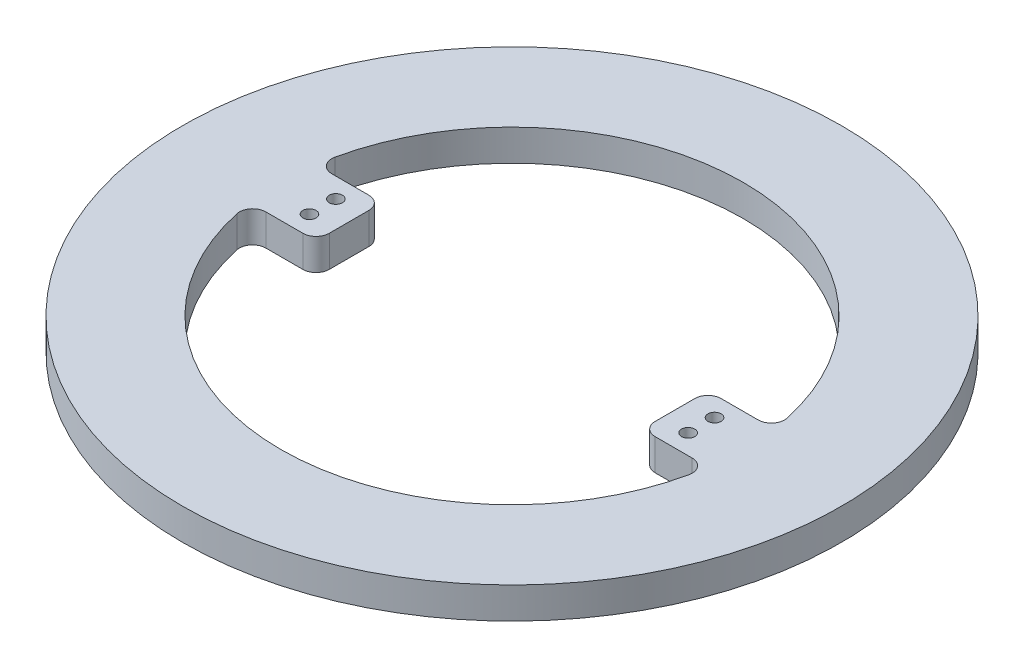
SolidWorks part; units mm, degrees
note: '?' marks a value the reader was unsure of.
ref_plane "Front Plane" through (0, 0, 0) normal (0, 0, 1) x (1, 0, 0)
ref_plane "Top Plane" through (0, 0, 0) normal (0, 1, 0) x (1, 0, 0)
ref_plane "Right Plane" through (0, 0, 0) normal (1, 0, 0) x (0, 0, -1)
sketch "Sketch1" plane through (0, 0, 0) normal (0, 1, 0) x (1, 0, 0)
  line L0 (0, -12.4783) -> (0, 12.4783) construction
  line L2 (-12.5, 0) -> (12.5, 0) construction
  line L6 (-32.3068, -5) -> (-26.6981, -5)
  line L7 (-49.95, 0) -> (49.95, 0) construction
  line L9 (0, 49.95) -> (0, -49.95) construction
  line L11 (-32.3068, 5) -> (-26.6981, 5)
  line L12 (-24.6981, 3) -> (-24.6981, -3)
  line L13 (24.6981, 3) -> (24.6981, -3)
  line L14 (26.6981, -5) -> (32.3068, -5)
  line L15 (26.6981, 5) -> (32.3068, 5)
  circle A0 centre (0, 0) radius 49.95
  arc A22 (-34.2615, -7.4235) -> (34.2615, -7.4235) centre (0, 0) ccw
  arc A23 (34.2615, 7.4235) -> (-34.2615, 7.4235) centre (0, 0) ccw
  arc A24 (32.3068, -5) -> (34.2615, -7.4235) centre (32.3068, -7) cw
  arc A25 (32.3068, 5) -> (34.2615, 7.4235) centre (32.3068, 7) ccw
  arc A26 (24.6981, 3) -> (26.6981, 5) centre (26.6981, 3) cw
  arc A27 (24.6981, -3) -> (26.6981, -5) centre (26.6981, -3) ccw
  arc A28 (-24.6981, 3) -> (-26.6981, 5) centre (-26.6981, 3) ccw
  arc A29 (-32.3068, 5) -> (-34.2615, 7.4235) centre (-32.3068, 7) cw
  arc A30 (-32.3068, -5) -> (-34.2615, -7.4235) centre (-32.3068, -7) ccw
  arc A31 (-24.6981, -3) -> (-26.6981, -5) centre (-26.6981, -3) cw
  circle A32 centre (-28.6981, -2) radius 1
  circle A33 centre (-28.6981, 2) radius 1
  circle A34 centre (28.6981, -2) radius 1
  circle A35 centre (28.6981, 2) radius 1
  point P7 (0, 0)
  point P12 (0, 0)
  point P20 (34.6981, -5)
  point P23 (34.6981, 5)
  point P26 (24.6981, 5)
  point P32 (24.6981, -5)
  point P35 (-24.6981, 5)
  point P38 (-34.6981, 5)
  point P41 (-34.6981, -5)
  point P44 (-24.6981, -5)
  dimension "D1" = 5
  dimension "D2" = 10
  dimension "D3" = 2
  dimension "D4" = 4
  dimension "D5" = 3
extrude "Boss-Extrude1" add sketch "Sketch1" along normal blind 4.75
sketch "Sketch2" plane through (0, 4.75, 0) normal (0, 1, 0) x (1, 0, 0)
  line L1 (0, 49.95) -> (0, -49.95) construction
  line L9 (-49.95, 0) -> (49.95, 0) construction
  circle A6 centre (0, 0) radius 49.95 construction
sketch "Sketch3" plane through (0, 4.75, 0) normal (0, 1, 0) x (1, 0, 0)
  line L0 (0, 35.0565) -> (0, 40.0565)
  line L1 (0.6118, 35.0511) -> (0.6991, 40.0504)
  line L2 (1.2235, 35.0351) -> (1.398, 40.0321)
  line L3 (1.8347, 35.0084) -> (2.0964, 40.0016)
  line L4 (2.4454, 34.9711) -> (2.7942, 39.9589)
  line L5 (3.0554, 34.9231) -> (3.4912, 39.9041)
  line L6 (3.6644, 34.8644) -> (4.187, 39.8371)
  line L7 (4.2723, 34.7952) -> (4.8817, 39.7579)
  line L8 (4.8789, 34.7153) -> (5.5748, 39.6667)
  line L9 (5.484, 34.6249) -> (6.2662, 39.5633)
  line L10 (6.0875, 34.5239) -> (6.9557, 39.4479)
  line L11 (6.6891, 34.4124) -> (7.6431, 39.3205)
  line L12 (7.2887, 34.2904) -> (8.3282, 39.1812)
  line L13 (7.886, 34.158) -> (9.0107, 39.0298)
  line L14 (8.4809, 34.0152) -> (9.6905, 38.8666)
  line L15 (9.0733, 33.862) -> (10.3674, 38.6916)
  line L16 (9.6629, 33.6985) -> (11.0411, 38.5048)
  line L17 (10.2495, 33.5247) -> (11.7114, 38.3062)
  line L18 (10.833, 33.3407) -> (12.3781, 38.096)
  line L19 (11.4133, 33.1466) -> (13.0411, 37.8742)
  line L20 (11.99, 32.9423) -> (13.7001, 37.6408)
  line L21 (12.5631, 32.728) -> (14.355, 37.396)
  line L22 (13.1324, 32.5038) -> (15.0054, 37.1397)
  line L23 (13.6977, 32.2697) -> (15.6513, 36.8722)
  line L24 (14.2588, 32.0257) -> (16.2924, 36.5934)
  line L25 (14.8155, 31.772) -> (16.9286, 36.3035)
  line L26 (15.3678, 31.5086) -> (17.5596, 36.0025)
  line L27 (15.9153, 31.2356) -> (18.1853, 35.6906)
  line L28 (16.458, 30.953) -> (18.8054, 35.3678)
  line L29 (16.9957, 30.6611) -> (19.4198, 35.0342)
  line L30 (17.5282, 30.3598) -> (20.0282, 34.6899)
  line L31 (18.0554, 30.0493) -> (20.6306, 34.3351)
  line L32 (18.5771, 29.7296) -> (21.2267, 33.9698)
  line L33 (19.0931, 29.4008) -> (21.8163, 33.5942)
  line L34 (19.6033, 29.0631) -> (22.3993, 33.2083)
  line L35 (20.1076, 28.7166) -> (22.9755, 32.8124)
  line L36 (20.6057, 28.3613) -> (23.5446, 32.4064)
  line L37 (21.0975, 27.9974) -> (24.1066, 31.9905)
  line L38 (21.5829, 27.6249) -> (24.6612, 31.5649)
  line L39 (22.0618, 27.244) -> (25.2084, 31.1297)
  line L40 (22.5339, 26.8548) -> (25.7478, 30.685)
  line L41 (22.9991, 26.4575) -> (26.2794, 30.231)
  line L42 (23.4574, 26.052) -> (26.803, 29.7678)
  line L43 (23.9085, 25.6387) -> (27.3185, 29.2955)
  line L44 (24.3523, 25.2175) -> (27.8256, 28.8142)
  line L45 (24.7887, 24.7887) -> (28.3242, 28.3242)
  line L46 (25.2175, 24.3523) -> (28.8142, 27.8256)
  line L47 (25.6387, 23.9085) -> (29.2955, 27.3185)
  line L48 (26.052, 23.4574) -> (29.7678, 26.803)
  line L49 (26.4575, 22.9991) -> (30.231, 26.2794)
  line L50 (26.8548, 22.5339) -> (30.685, 25.7478)
  line L51 (27.244, 22.0618) -> (31.1297, 25.2084)
  line L52 (27.6249, 21.5829) -> (31.5649, 24.6612)
  line L53 (27.9974, 21.0975) -> (31.9905, 24.1066)
  line L54 (28.3613, 20.6057) -> (32.4064, 23.5446)
  line L55 (28.7166, 20.1076) -> (32.8124, 22.9755)
  line L56 (29.0631, 19.6033) -> (33.2083, 22.3993)
  line L57 (29.4008, 19.0931) -> (33.5942, 21.8163)
  line L58 (29.7296, 18.5771) -> (33.9698, 21.2267)
  line L59 (30.0493, 18.0554) -> (34.3351, 20.6306)
  line L60 (30.3598, 17.5282) -> (34.6899, 20.0282)
  line L61 (30.6611, 16.9957) -> (35.0342, 19.4198)
  line L62 (30.953, 16.458) -> (35.3678, 18.8054)
  line L63 (31.2356, 15.9153) -> (35.6906, 18.1853)
  line L64 (31.5086, 15.3678) -> (36.0025, 17.5596)
  line L65 (31.772, 14.8155) -> (36.3035, 16.9286)
  line L66 (32.0257, 14.2588) -> (36.5934, 16.2924)
  line L67 (32.2697, 13.6977) -> (36.8722, 15.6513)
  line L68 (32.5038, 13.1324) -> (37.1397, 15.0054)
  line L69 (32.728, 12.5631) -> (37.396, 14.355)
  line L70 (32.9423, 11.99) -> (37.6408, 13.7001)
  line L71 (33.1466, 11.4133) -> (37.8742, 13.0411)
  line L72 (33.3407, 10.833) -> (38.096, 12.3781)
  line L73 (33.5247, 10.2495) -> (38.3062, 11.7114)
  line L74 (33.6985, 9.6629) -> (38.5048, 11.0411)
  line L75 (33.862, 9.0733) -> (38.6916, 10.3674)
  line L76 (34.0152, 8.4809) -> (38.8666, 9.6905)
  line L77 (34.158, 7.886) -> (39.0298, 9.0107)
  line L78 (34.2904, 7.2887) -> (39.1812, 8.3282)
  line L79 (34.4124, 6.6891) -> (39.3205, 7.6431)
  line L80 (34.5239, 6.0875) -> (39.4479, 6.9557)
  line L81 (34.6249, 5.484) -> (39.5633, 6.2662)
  line L82 (34.7153, 4.8789) -> (39.6667, 5.5748)
  line L83 (34.7952, 4.2723) -> (39.7579, 4.8817)
  line L84 (34.8644, 3.6644) -> (39.8371, 4.187)
  line L85 (34.9231, 3.0554) -> (39.9041, 3.4912)
  line L86 (34.9711, 2.4454) -> (39.9589, 2.7942)
  line L87 (35.0084, 1.8347) -> (40.0016, 2.0964)
  line L88 (35.0351, 1.2235) -> (40.0321, 1.398)
  line L89 (35.0511, 0.6118) -> (40.0504, 0.6991)
  line L90 (35.0565, 0) -> (40.0565, 0)
  line L91 (35.0511, -0.6118) -> (40.0504, -0.6991)
  line L92 (35.0351, -1.2235) -> (40.0321, -1.398)
  line L93 (35.0084, -1.8347) -> (40.0016, -2.0964)
  line L94 (34.9711, -2.4454) -> (39.9589, -2.7942)
  line L95 (34.9231, -3.0554) -> (39.9041, -3.4912)
  line L96 (34.8644, -3.6644) -> (39.8371, -4.187)
  line L97 (34.7952, -4.2723) -> (39.7579, -4.8817)
  line L98 (34.7153, -4.8789) -> (39.6667, -5.5748)
  line L99 (34.6249, -5.484) -> (39.5633, -6.2662)
  line L100 (34.5239, -6.0875) -> (39.4479, -6.9557)
  line L101 (34.4124, -6.6891) -> (39.3205, -7.6431)
  line L102 (34.2904, -7.2887) -> (39.1812, -8.3282)
  line L103 (34.158, -7.886) -> (39.0298, -9.0107)
  line L104 (34.0152, -8.4809) -> (38.8666, -9.6905)
  line L105 (33.862, -9.0733) -> (38.6916, -10.3674)
  line L106 (33.6985, -9.6629) -> (38.5048, -11.0411)
  line L107 (33.5247, -10.2495) -> (38.3062, -11.7114)
  line L108 (33.3407, -10.833) -> (38.096, -12.3781)
  line L109 (33.1466, -11.4133) -> (37.8742, -13.0411)
  line L110 (32.9423, -11.99) -> (37.6408, -13.7001)
  line L111 (32.728, -12.5631) -> (37.396, -14.355)
  line L112 (32.5038, -13.1324) -> (37.1397, -15.0054)
  line L113 (32.2697, -13.6977) -> (36.8722, -15.6513)
  line L114 (32.0257, -14.2588) -> (36.5934, -16.2924)
  line L115 (31.772, -14.8155) -> (36.3035, -16.9286)
  line L116 (31.5086, -15.3678) -> (36.0025, -17.5596)
  line L117 (31.2356, -15.9153) -> (35.6906, -18.1853)
  line L118 (30.953, -16.458) -> (35.3678, -18.8054)
  line L119 (30.6611, -16.9957) -> (35.0342, -19.4198)
  line L120 (30.3598, -17.5282) -> (34.6899, -20.0282)
  line L121 (30.0493, -18.0554) -> (34.3351, -20.6306)
  line L122 (29.7296, -18.5771) -> (33.9698, -21.2267)
  line L123 (29.4008, -19.0931) -> (33.5942, -21.8163)
  line L124 (29.0631, -19.6033) -> (33.2083, -22.3993)
  line L125 (28.7166, -20.1076) -> (32.8124, -22.9755)
  line L126 (28.3613, -20.6057) -> (32.4064, -23.5446)
  line L127 (27.9974, -21.0975) -> (31.9905, -24.1066)
  line L128 (27.6249, -21.5829) -> (31.5649, -24.6612)
  line L129 (27.244, -22.0618) -> (31.1297, -25.2084)
  line L130 (26.8548, -22.5339) -> (30.685, -25.7478)
  line L131 (26.4575, -22.9991) -> (30.231, -26.2794)
  line L132 (26.052, -23.4574) -> (29.7678, -26.803)
  line L133 (25.6387, -23.9085) -> (29.2955, -27.3185)
  line L134 (25.2175, -24.3523) -> (28.8142, -27.8256)
  line L135 (24.7887, -24.7887) -> (28.3242, -28.3242)
  line L136 (24.3523, -25.2175) -> (27.8256, -28.8142)
  line L137 (23.9085, -25.6387) -> (27.3185, -29.2955)
  line L138 (23.4574, -26.052) -> (26.803, -29.7678)
  line L139 (22.9991, -26.4575) -> (26.2794, -30.231)
  line L140 (22.5339, -26.8548) -> (25.7478, -30.685)
  line L141 (22.0618, -27.244) -> (25.2084, -31.1297)
  line L142 (21.5829, -27.6249) -> (24.6612, -31.5649)
  line L143 (21.0975, -27.9974) -> (24.1066, -31.9905)
  line L144 (20.6057, -28.3613) -> (23.5446, -32.4064)
  line L145 (20.1076, -28.7166) -> (22.9755, -32.8124)
  line L146 (19.6033, -29.0631) -> (22.3993, -33.2083)
  line L147 (19.0931, -29.4008) -> (21.8163, -33.5942)
  line L148 (18.5771, -29.7296) -> (21.2267, -33.9698)
  line L149 (18.0554, -30.0493) -> (20.6306, -34.3351)
  line L150 (17.5282, -30.3598) -> (20.0282, -34.6899)
  line L151 (16.9957, -30.6611) -> (19.4198, -35.0342)
  line L152 (16.458, -30.953) -> (18.8054, -35.3678)
  line L153 (15.9153, -31.2356) -> (18.1853, -35.6906)
  line L154 (15.3678, -31.5086) -> (17.5596, -36.0025)
  line L155 (14.8155, -31.772) -> (16.9286, -36.3035)
  line L156 (14.2588, -32.0257) -> (16.2924, -36.5934)
  line L157 (13.6977, -32.2697) -> (15.6513, -36.8722)
  line L158 (13.1324, -32.5038) -> (15.0054, -37.1397)
  line L159 (12.5631, -32.728) -> (14.355, -37.396)
  line L160 (11.99, -32.9423) -> (13.7001, -37.6408)
  line L161 (11.4133, -33.1466) -> (13.0411, -37.8742)
  line L162 (10.833, -33.3407) -> (12.3781, -38.096)
  line L163 (10.2495, -33.5247) -> (11.7114, -38.3062)
  line L164 (9.6629, -33.6985) -> (11.0411, -38.5048)
  line L165 (9.0733, -33.862) -> (10.3674, -38.6916)
  line L166 (8.4809, -34.0152) -> (9.6905, -38.8666)
  line L167 (7.886, -34.158) -> (9.0107, -39.0298)
  line L168 (7.2887, -34.2904) -> (8.3282, -39.1812)
  line L169 (6.6891, -34.4124) -> (7.6431, -39.3205)
  line L170 (6.0875, -34.5239) -> (6.9557, -39.4479)
  line L171 (5.484, -34.6249) -> (6.2662, -39.5633)
  line L172 (4.8789, -34.7153) -> (5.5748, -39.6667)
  line L173 (4.2723, -34.7952) -> (4.8817, -39.7579)
  line L174 (3.6644, -34.8644) -> (4.187, -39.8371)
  line L175 (3.0554, -34.9231) -> (3.4912, -39.9041)
  line L176 (2.4454, -34.9711) -> (2.7942, -39.9589)
  line L177 (1.8347, -35.0084) -> (2.0964, -40.0016)
  line L178 (1.2235, -35.0351) -> (1.398, -40.0321)
  line L179 (0.6118, -35.0511) -> (0.6991, -40.0504)
  line L180 (0, -35.0565) -> (0, -40.0565)
  line L181 (-0.6118, -35.0511) -> (-0.6991, -40.0504)
  line L182 (-1.2235, -35.0351) -> (-1.398, -40.0321)
  line L183 (-1.8347, -35.0084) -> (-2.0964, -40.0016)
  line L184 (-2.4454, -34.9711) -> (-2.7942, -39.9589)
  line L185 (-3.0554, -34.9231) -> (-3.4912, -39.9041)
  line L186 (-3.6644, -34.8644) -> (-4.187, -39.8371)
  line L187 (-4.2723, -34.7952) -> (-4.8817, -39.7579)
  line L188 (-4.8789, -34.7153) -> (-5.5748, -39.6667)
  line L189 (-5.484, -34.6249) -> (-6.2662, -39.5633)
  line L190 (-6.0875, -34.5239) -> (-6.9557, -39.4479)
  line L191 (-6.6891, -34.4124) -> (-7.6431, -39.3205)
  line L192 (-7.2887, -34.2904) -> (-8.3282, -39.1812)
  line L193 (-7.886, -34.158) -> (-9.0107, -39.0298)
  line L194 (-8.4809, -34.0152) -> (-9.6905, -38.8666)
  line L195 (-9.0733, -33.862) -> (-10.3674, -38.6916)
  line L196 (-9.6629, -33.6985) -> (-11.0411, -38.5048)
  line L197 (-10.2495, -33.5247) -> (-11.7114, -38.3062)
  line L198 (-10.833, -33.3407) -> (-12.3781, -38.096)
  line L199 (-11.4133, -33.1466) -> (-13.0411, -37.8742)
  line L200 (-11.99, -32.9423) -> (-13.7001, -37.6408)
  line L201 (-12.5631, -32.728) -> (-14.355, -37.396)
  line L202 (-13.1324, -32.5038) -> (-15.0054, -37.1397)
  line L203 (-13.6977, -32.2697) -> (-15.6513, -36.8722)
  line L204 (-14.2588, -32.0257) -> (-16.2924, -36.5934)
  line L205 (-14.8155, -31.772) -> (-16.9286, -36.3035)
  line L206 (-15.3678, -31.5086) -> (-17.5596, -36.0025)
  line L207 (-15.9153, -31.2356) -> (-18.1853, -35.6906)
  line L208 (-16.458, -30.953) -> (-18.8054, -35.3678)
  line L209 (-16.9957, -30.6611) -> (-19.4198, -35.0342)
  line L210 (-17.5282, -30.3598) -> (-20.0282, -34.6899)
  line L211 (-18.0554, -30.0493) -> (-20.6306, -34.3351)
  line L212 (-18.5771, -29.7296) -> (-21.2267, -33.9698)
  line L213 (-19.0931, -29.4008) -> (-21.8163, -33.5942)
  line L214 (-19.6033, -29.0631) -> (-22.3993, -33.2083)
  line L215 (-20.1076, -28.7166) -> (-22.9755, -32.8124)
  line L216 (-20.6057, -28.3613) -> (-23.5446, -32.4064)
  line L217 (-21.0975, -27.9974) -> (-24.1066, -31.9905)
  line L218 (-21.5829, -27.6249) -> (-24.6612, -31.5649)
  line L219 (-22.0618, -27.244) -> (-25.2084, -31.1297)
  line L220 (-22.5339, -26.8548) -> (-25.7478, -30.685)
  line L221 (-22.9991, -26.4575) -> (-26.2794, -30.231)
  line L222 (-23.4574, -26.052) -> (-26.803, -29.7678)
  line L223 (-23.9085, -25.6387) -> (-27.3185, -29.2955)
  line L224 (-24.3523, -25.2175) -> (-27.8256, -28.8142)
  line L225 (-24.7887, -24.7887) -> (-28.3242, -28.3242)
  line L226 (-25.2175, -24.3523) -> (-28.8142, -27.8256)
  line L227 (-25.6387, -23.9085) -> (-29.2955, -27.3185)
  line L228 (-26.052, -23.4574) -> (-29.7678, -26.803)
  line L229 (-26.4575, -22.9991) -> (-30.231, -26.2794)
  line L230 (-26.8548, -22.5339) -> (-30.685, -25.7478)
  line L231 (-27.244, -22.0618) -> (-31.1297, -25.2084)
  line L232 (-27.6249, -21.5829) -> (-31.5649, -24.6612)
  line L233 (-27.9974, -21.0975) -> (-31.9905, -24.1066)
  line L234 (-28.3613, -20.6057) -> (-32.4064, -23.5446)
  line L235 (-28.7166, -20.1076) -> (-32.8124, -22.9755)
  line L236 (-29.0631, -19.6033) -> (-33.2083, -22.3993)
  line L237 (-29.4008, -19.0931) -> (-33.5942, -21.8163)
  line L238 (-29.7296, -18.5771) -> (-33.9698, -21.2267)
  line L239 (-30.0493, -18.0554) -> (-34.3351, -20.6306)
  line L240 (-30.3598, -17.5282) -> (-34.6899, -20.0282)
  line L241 (-30.6611, -16.9957) -> (-35.0342, -19.4198)
  line L242 (-30.953, -16.458) -> (-35.3678, -18.8054)
  line L243 (-31.2356, -15.9153) -> (-35.6906, -18.1853)
  line L244 (-31.5086, -15.3678) -> (-36.0025, -17.5596)
  line L245 (-31.772, -14.8155) -> (-36.3035, -16.9286)
  line L246 (-32.0257, -14.2588) -> (-36.5934, -16.2924)
  line L247 (-32.2697, -13.6977) -> (-36.8722, -15.6513)
  line L248 (-32.5038, -13.1324) -> (-37.1397, -15.0054)
  line L249 (-32.728, -12.5631) -> (-37.396, -14.355)
  line L250 (-32.9423, -11.99) -> (-37.6408, -13.7001)
  line L251 (-33.1466, -11.4133) -> (-37.8742, -13.0411)
  line L252 (-33.3407, -10.833) -> (-38.096, -12.3781)
  line L253 (-33.5247, -10.2495) -> (-38.3062, -11.7114)
  line L254 (-33.6985, -9.6629) -> (-38.5048, -11.0411)
  line L255 (-33.862, -9.0733) -> (-38.6916, -10.3674)
  line L256 (-34.0152, -8.4809) -> (-38.8666, -9.6905)
  line L257 (-34.158, -7.886) -> (-39.0298, -9.0107)
  line L258 (-34.2904, -7.2887) -> (-39.1812, -8.3282)
  line L259 (-34.4124, -6.6891) -> (-39.3205, -7.6431)
  line L260 (-34.5239, -6.0875) -> (-39.4479, -6.9557)
  line L261 (-34.6249, -5.484) -> (-39.5633, -6.2662)
  line L262 (-34.7153, -4.8789) -> (-39.6667, -5.5748)
  line L263 (-34.7952, -4.2723) -> (-39.7579, -4.8817)
  line L264 (-34.8644, -3.6644) -> (-39.8371, -4.187)
  line L265 (-34.9231, -3.0554) -> (-39.9041, -3.4912)
  line L266 (-34.9711, -2.4454) -> (-39.9589, -2.7942)
  line L267 (-35.0084, -1.8347) -> (-40.0016, -2.0964)
  line L268 (-35.0351, -1.2235) -> (-40.0321, -1.398)
  line L269 (-35.0511, -0.6118) -> (-40.0504, -0.6991)
  line L270 (-35.0565, 0) -> (-40.0565, 0)
  line L271 (-35.0511, 0.6118) -> (-40.0504, 0.6991)
  line L272 (-35.0351, 1.2235) -> (-40.0321, 1.398)
  line L273 (-35.0084, 1.8347) -> (-40.0016, 2.0964)
  line L274 (-34.9711, 2.4454) -> (-39.9589, 2.7942)
  line L275 (-34.9231, 3.0554) -> (-39.9041, 3.4912)
  line L276 (-34.8644, 3.6644) -> (-39.8371, 4.187)
  line L277 (-34.7952, 4.2723) -> (-39.7579, 4.8817)
  line L278 (-34.7153, 4.8789) -> (-39.6667, 5.5748)
  line L279 (-34.6249, 5.484) -> (-39.5633, 6.2662)
  line L280 (-34.5239, 6.0875) -> (-39.4479, 6.9557)
  line L281 (-34.4124, 6.6891) -> (-39.3205, 7.6431)
  line L282 (-34.2904, 7.2887) -> (-39.1812, 8.3282)
  line L283 (-34.158, 7.886) -> (-39.0298, 9.0107)
  line L284 (-34.0152, 8.4809) -> (-38.8666, 9.6905)
  line L285 (-33.862, 9.0733) -> (-38.6916, 10.3674)
  line L286 (-33.6985, 9.6629) -> (-38.5048, 11.0411)
  line L287 (-33.5247, 10.2495) -> (-38.3062, 11.7114)
  line L288 (-33.3407, 10.833) -> (-38.096, 12.3781)
  line L289 (-33.1466, 11.4133) -> (-37.8742, 13.0411)
  line L290 (-32.9423, 11.99) -> (-37.6408, 13.7001)
  line L291 (-32.728, 12.5631) -> (-37.396, 14.355)
  line L292 (-32.5038, 13.1324) -> (-37.1397, 15.0054)
  line L293 (-32.2697, 13.6977) -> (-36.8722, 15.6513)
  line L294 (-32.0257, 14.2588) -> (-36.5934, 16.2924)
  line L295 (-31.772, 14.8155) -> (-36.3035, 16.9286)
  line L296 (-31.5086, 15.3678) -> (-36.0025, 17.5596)
  line L297 (-31.2356, 15.9153) -> (-35.6906, 18.1853)
  line L298 (-30.953, 16.458) -> (-35.3678, 18.8054)
  line L299 (-30.6611, 16.9957) -> (-35.0342, 19.4198)
  line L300 (-30.3598, 17.5282) -> (-34.6899, 20.0282)
  line L301 (-30.0493, 18.0554) -> (-34.3351, 20.6306)
  line L302 (-29.7296, 18.5771) -> (-33.9698, 21.2267)
  line L303 (-29.4008, 19.0931) -> (-33.5942, 21.8163)
  line L304 (-29.0631, 19.6033) -> (-33.2083, 22.3993)
  line L305 (-28.7166, 20.1076) -> (-32.8124, 22.9755)
  line L306 (-28.3613, 20.6057) -> (-32.4064, 23.5446)
  line L307 (-27.9974, 21.0975) -> (-31.9905, 24.1066)
  line L308 (-27.6249, 21.5829) -> (-31.5649, 24.6612)
  line L309 (-27.244, 22.0618) -> (-31.1297, 25.2084)
  line L310 (-26.8548, 22.5339) -> (-30.685, 25.7478)
  line L311 (-26.4575, 22.9991) -> (-30.231, 26.2794)
  line L312 (-26.052, 23.4574) -> (-29.7678, 26.803)
  line L313 (-25.6387, 23.9085) -> (-29.2955, 27.3185)
  line L314 (-25.2175, 24.3523) -> (-28.8142, 27.8256)
  line L315 (-24.7887, 24.7887) -> (-28.3242, 28.3242)
  line L316 (-24.3523, 25.2175) -> (-27.8256, 28.8142)
  line L317 (-23.9085, 25.6387) -> (-27.3185, 29.2955)
  line L318 (-23.4574, 26.052) -> (-26.803, 29.7678)
  line L319 (-22.9991, 26.4575) -> (-26.2794, 30.231)
  line L320 (-22.5339, 26.8548) -> (-25.7478, 30.685)
  line L321 (-22.0618, 27.244) -> (-25.2084, 31.1297)
  line L322 (-21.5829, 27.6249) -> (-24.6612, 31.5649)
  line L323 (-21.0975, 27.9974) -> (-24.1066, 31.9905)
  line L324 (-20.6057, 28.3613) -> (-23.5446, 32.4064)
  line L325 (-20.1076, 28.7166) -> (-22.9755, 32.8124)
  line L326 (-19.6033, 29.0631) -> (-22.3993, 33.2083)
  line L327 (-19.0931, 29.4008) -> (-21.8163, 33.5942)
  line L328 (-18.5771, 29.7296) -> (-21.2267, 33.9698)
  line L329 (-18.0554, 30.0493) -> (-20.6306, 34.3351)
  line L330 (-17.5282, 30.3598) -> (-20.0282, 34.6899)
  line L331 (-16.9957, 30.6611) -> (-19.4198, 35.0342)
  line L332 (-16.458, 30.953) -> (-18.8054, 35.3678)
  line L333 (-15.9153, 31.2356) -> (-18.1853, 35.6906)
  line L334 (-15.3678, 31.5086) -> (-17.5596, 36.0025)
  line L335 (-14.8155, 31.772) -> (-16.9286, 36.3035)
  line L336 (-14.2588, 32.0257) -> (-16.2924, 36.5934)
  line L337 (-13.6977, 32.2697) -> (-15.6513, 36.8722)
  line L338 (-13.1324, 32.5038) -> (-15.0054, 37.1397)
  line L339 (-12.5631, 32.728) -> (-14.355, 37.396)
  line L340 (-11.99, 32.9423) -> (-13.7001, 37.6408)
  line L341 (-11.4133, 33.1466) -> (-13.0411, 37.8742)
  line L342 (-10.833, 33.3407) -> (-12.3781, 38.096)
  line L343 (-10.2495, 33.5247) -> (-11.7114, 38.3062)
  line L344 (-9.6629, 33.6985) -> (-11.0411, 38.5048)
  line L345 (-9.0733, 33.862) -> (-10.3674, 38.6916)
  line L346 (-8.4809, 34.0152) -> (-9.6905, 38.8666)
  line L347 (-7.886, 34.158) -> (-9.0107, 39.0298)
  line L348 (-7.2887, 34.2904) -> (-8.3282, 39.1812)
  line L349 (-6.6891, 34.4124) -> (-7.6431, 39.3205)
  line L350 (-6.0875, 34.5239) -> (-6.9557, 39.4479)
  line L351 (-5.484, 34.6249) -> (-6.2662, 39.5633)
  line L352 (-4.8789, 34.7153) -> (-5.5748, 39.6667)
  line L353 (-4.2723, 34.7952) -> (-4.8817, 39.7579)
  line L354 (-3.6644, 34.8644) -> (-4.187, 39.8371)
  line L355 (-3.0554, 34.9231) -> (-3.4912, 39.9041)
  line L356 (-2.4454, 34.9711) -> (-2.7942, 39.9589)
  line L357 (-1.8347, 35.0084) -> (-2.0964, 40.0016)
  line L358 (-1.2235, 35.0351) -> (-1.398, 40.0321)
  line L359 (-0.6118, 35.0511) -> (-0.6991, 40.0504)
  line L360 (0, 40.0565) -> (0, 42.0565)
  line L361 (3.4912, 39.9041) -> (3.6655, 41.8964)
  line L362 (6.9557, 39.4479) -> (7.303, 41.4176)
  line L363 (10.3674, 38.6916) -> (10.885, 40.6234)
  line L364 (13.7001, 37.6408) -> (14.3842, 39.5202)
  line L365 (16.9286, 36.3035) -> (17.7738, 38.1161)
  line L366 (20.0282, 34.6899) -> (21.0282, 36.422)
  line L367 (22.9755, 32.8124) -> (24.1226, 34.4507)
  line L368 (25.7478, 30.685) -> (27.0334, 32.2171)
  line L369 (28.3242, 28.3242) -> (29.7384, 29.7384)
  line L370 (30.685, 25.7478) -> (32.2171, 27.0334)
  line L371 (32.8124, 22.9755) -> (34.4507, 24.1226)
  line L372 (34.6899, 20.0282) -> (36.422, 21.0282)
  line L373 (36.3035, 16.9286) -> (38.1161, 17.7738)
  line L374 (37.6408, 13.7001) -> (39.5202, 14.3842)
  line L375 (38.6916, 10.3674) -> (40.6234, 10.885)
  line L376 (39.4479, 6.9557) -> (41.4176, 7.303)
  line L377 (39.9041, 3.4912) -> (41.8964, 3.6655)
  line L378 (40.0565, 0) -> (42.0565, 0)
  line L379 (39.9041, -3.4912) -> (41.8964, -3.6655)
  line L380 (39.4479, -6.9557) -> (41.4176, -7.303)
  line L381 (38.6916, -10.3674) -> (40.6234, -10.885)
  line L382 (37.6408, -13.7001) -> (39.5202, -14.3842)
  line L383 (36.3035, -16.9286) -> (38.1161, -17.7738)
  line L384 (34.6899, -20.0282) -> (36.422, -21.0282)
  line L385 (32.8124, -22.9755) -> (34.4507, -24.1226)
  line L386 (30.685, -25.7478) -> (32.2171, -27.0334)
  line L387 (28.3242, -28.3242) -> (29.7384, -29.7384)
  line L388 (25.7478, -30.685) -> (27.0334, -32.2171)
  line L389 (22.9755, -32.8124) -> (24.1226, -34.4507)
  line L390 (20.0282, -34.6899) -> (21.0282, -36.422)
  line L391 (16.9286, -36.3035) -> (17.7738, -38.1161)
  line L392 (13.7001, -37.6408) -> (14.3842, -39.5202)
  line L393 (10.3674, -38.6916) -> (10.885, -40.6234)
  line L394 (6.9557, -39.4479) -> (7.303, -41.4176)
  line L395 (3.4912, -39.9041) -> (3.6655, -41.8964)
  line L396 (0, -40.0565) -> (0, -42.0565)
  line L397 (-3.4912, -39.9041) -> (-3.6655, -41.8964)
  line L398 (-6.9557, -39.4479) -> (-7.303, -41.4176)
  line L399 (-10.3674, -38.6916) -> (-10.885, -40.6234)
  line L400 (-13.7001, -37.6408) -> (-14.3842, -39.5202)
  line L401 (-16.9286, -36.3035) -> (-17.7738, -38.1161)
  line L402 (-20.0282, -34.6899) -> (-21.0282, -36.422)
  line L403 (-22.9755, -32.8124) -> (-24.1226, -34.4507)
  line L404 (-25.7478, -30.685) -> (-27.0334, -32.2171)
  line L405 (-28.3242, -28.3242) -> (-29.7384, -29.7384)
  line L406 (-30.685, -25.7478) -> (-32.2171, -27.0334)
  line L407 (-32.8124, -22.9755) -> (-34.4507, -24.1226)
  line L408 (-34.6899, -20.0282) -> (-36.422, -21.0282)
  line L409 (-36.3035, -16.9286) -> (-38.1161, -17.7738)
  line L410 (-37.6408, -13.7001) -> (-39.5202, -14.3842)
  line L411 (-38.6916, -10.3674) -> (-40.6234, -10.885)
  line L412 (-39.4479, -6.9557) -> (-41.4176, -7.303)
  line L413 (-39.9041, -3.4912) -> (-41.8964, -3.6655)
  line L414 (-40.0565, 0) -> (-42.0565, 0)
  line L415 (-39.9041, 3.4912) -> (-41.8964, 3.6655)
  line L416 (-39.4479, 6.9557) -> (-41.4176, 7.303)
  line L417 (-38.6916, 10.3674) -> (-40.6234, 10.885)
  line L418 (-37.6408, 13.7001) -> (-39.5202, 14.3842)
  line L419 (-36.3035, 16.9286) -> (-38.1161, 17.7738)
  line L420 (-34.6899, 20.0282) -> (-36.422, 21.0282)
  line L421 (-32.8124, 22.9755) -> (-34.4507, 24.1226)
  line L422 (-30.685, 25.7478) -> (-32.2171, 27.0334)
  line L423 (-28.3242, 28.3242) -> (-29.7384, 29.7384)
  line L424 (-25.7478, 30.685) -> (-27.0334, 32.2171)
  line L425 (-22.9755, 32.8124) -> (-24.1226, 34.4507)
  line L426 (-20.0282, 34.6899) -> (-21.0282, 36.422)
  line L427 (-16.9286, 36.3035) -> (-17.7738, 38.1161)
  line L428 (-13.7001, 37.6408) -> (-14.3842, 39.5202)
  line L429 (-10.3674, 38.6916) -> (-10.885, 40.6234)
  line L430 (-6.9557, 39.4479) -> (-7.303, 41.4176)
  line L431 (-3.4912, 39.9041) -> (-3.6655, 41.8964)
  line L432 (-6, 40.0565) -> (6, 40.0565) construction
  line L433 (-49.95, 0) -> (49.95, 0) construction
  line L434 (0, 49.95) -> (0, -49.95) construction
  line L435 (-6, -40.0565) -> (6, -40.0565) construction
  line L436 (-40.0565, -6) -> (-40.0565, 6) construction
  line L437 (40.0565, -6) -> (40.0565, 6) construction
  arc A0 (34.2615, 7.4235) -> (-34.2615, 7.4235) centre (0, 0) ccw construction
  circle A1 centre (0, 0) radius 49.95 construction
  text T0 "270°"
  text T1 "0°"
  text T2 "90°"
  text T3 "180°"
  point P728 (0, 0)
  point P737 (0, 40.0565)
  point P871 (0, 0)
  dimension "D1" = 360
convert to sheet metal "Convert-Solid1" [suppressed] bend radius? 10 thickness? 4.75
sketch "Bend-Lines1" [suppressed] plane through (0, 0, 0) normal (0, 1, 0) x (1, 0, 0)
sketch "Bounding-Box1" [suppressed] plane through (0, 0, 0) normal (0, 1, 0) x (1, 0, 0)
sheet metal parameters "Sheet-Metal5" thickness 4.75 parameters "D1"=10
flat pattern "Flat-Pattern5" [suppressed]
sketch "Bend-Lines2" [suppressed] plane through (0, 0, 0) normal (0, 1, 0) x (1, 0, 0)
sketch3d "Bounding-Box2" [suppressed]
  line L0 (50, -49.8999, 0) -> (-49.9, -49.9999, 0) construction
  line L1 (49.9, 50, 0) -> (-50, 49.9, 0) construction
  line L2 (50, -49.8999, 0) -> (49.9, 50, 0) construction
  line L3 (-49.9, -49.9999, 0) -> (-50, 49.9, 0) construction
